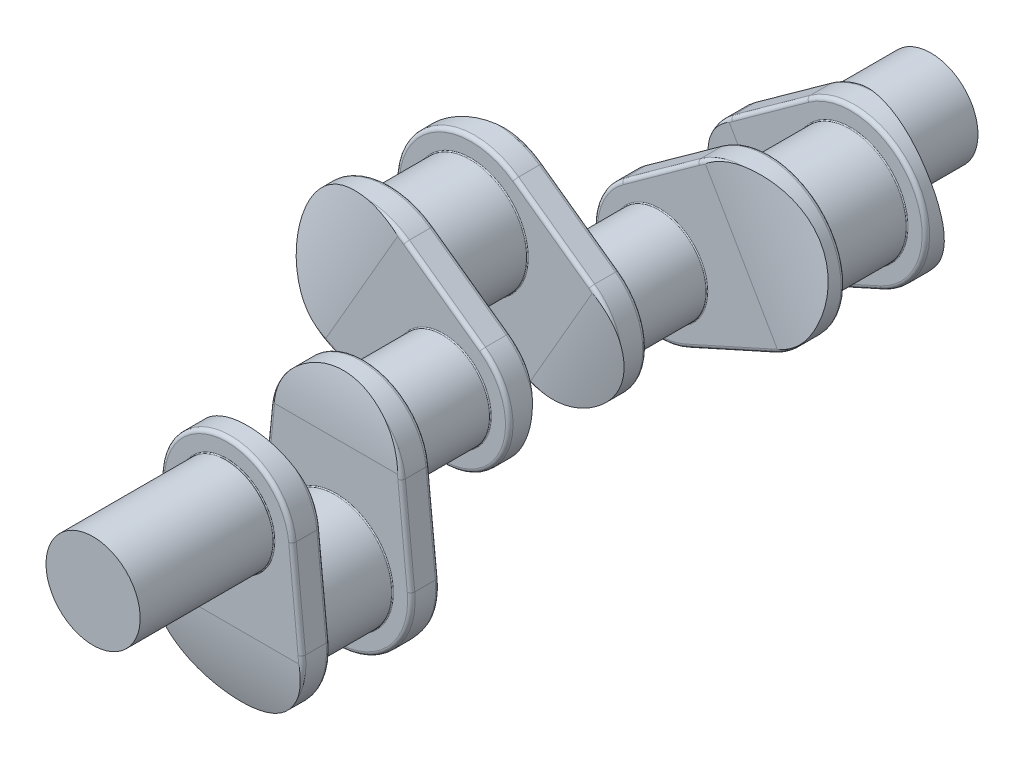
SolidWorks part; units mm, degrees
ref_plane "Front Plane" through (0, 0, 0) normal (0, 0, 1) x (1, 0, 0)
ref_plane "Top Plane" through (0, 0, 0) normal (0, 1, 0) x (1, 0, 0)
ref_plane "Right Plane" through (0, 0, 0) normal (1, 0, 0) x (0, 0, -1)
sketch "Sketch1" plane through (0, 0, 0) normal (0, 0, 1) x (1, 0, 0)
  circle A0 centre (0, 0) radius 38.1
  dimension "D1" = 76.2
extrude "Boss-Extrude1" add sketch "Sketch1" along normal blind 27.31
sketch "Sketch2" plane through (0, 0, 27.31) normal (0, 0, 1) x (1, 0, 0)
  line L0 (44.2272, 67.945) -> (50.5454, 5.08)
  line L1 (-44.2272, 67.945) -> (-50.5454, 5.08)
  arc A0 (-50.5454, 5.08) -> (50.5454, 5.08) centre (0, 0) ccw
  arc A1 (44.2272, 67.945) -> (-44.2272, 67.945) centre (0, 63.5) ccw
  circle A2 centre (0, 0) radius 38.1 construction
  point P11 (0, 0)
  dimension "D1" = 12.7
  dimension "D2" = 88.9
  dimension "D3" = 63.5
extrude "Boss-Extrude2" add sketch "Sketch2" along normal blind 19
sketch "Sketch3" plane through (0, 0, 46.31) normal (0, 0, 1) x (1, 0, 0)
  circle A0 centre (0, 63.5) radius 31.75
  dimension "D1" = 63.5
extrude "Boss-Extrude3" add sketch "Sketch3" along normal blind 26.67
sketch "Sketch4" plane through (0, 0, 0) normal (1, 0, 0) x (0, 0, -1)
  line L0 (-46.31, 0) -> (-27.31, 0) construction
  line L1 (-46.31, 5.08) -> (-46.31, -50.8) construction
  line L2 (-46.31, -50.8) -> (-27.31, -50.8) construction
  line L3 (-46.31, 0) -> (-60.4648, 0)
  line L4 (-60.4648, 0) -> (-60.4648, -50.8)
  line L5 (-60.4648, -50.8) -> (-36.81, -50.8)
  line L6 (-46.31, 63.5) -> (-27.31, 63.5) construction
  line L7 (-27.31, 107.95) -> (-46.31, 107.95) construction
  line L8 (-27.31, 67.945) -> (-27.31, 107.95) construction
  line L9 (-27.31, 63.5) -> (-17.3681, 63.5)
  line L10 (-17.3681, 63.5) -> (-17.3681, 107.95)
  line L11 (-17.3681, 107.95) -> (-32.31, 107.95)
  arc A0 (-46.31, 0) -> (-36.81, -50.8) centre (122.6069, 5.3005) ccw
  arc A1 (-27.31, 63.5) -> (-32.31, 107.95) centre (-196.2738, 67.0002) ccw
  dimension "D1" = 169
  dimension "D3" = 169
  dimension "D2" = 5
extrude "Cut-Extrude1" cut sketch "Sketch4" against normal through all both and the other way through all
fillet "Fillet1" radius 0.64 2 edges at (38.1, 0, 27.31) (31.75, 63.5, 46.31)
fillet "Fillet2" radius 2.54 10 edges at (50.7363, 2.5432, 46.31) (-50.7363, 2.5432, 46.31) (-47.3863, 36.5125, 46.31) (0, 107.95, 46.31) (-44.0798, 69.2251, 27.31) (-47.3863, 36.5125, 27.31) (0, -50.8, 27.31) (44.0798, 69.2251, 27.31) (47.3863, 36.5125, 46.31) (47.3863, 36.5125, 27.31)
mirror "Mirror2" about plane through (0, 0, 0) normal (0, 0, 1) of "Fillet2", "Fillet1", "Cut-Extrude1", "Boss-Extrude3", "Boss-Extrude2", "Boss-Extrude1"
pattern_linear "LPattern1" count 3 spacing 145.96 along (0, 0, -1) of bodies 117
ref_axis "Axis1" through (0, 63.5, 166.4472) along (0, 0, -1)
move or copy body "Body-Move/Copy1" bodies to move or copy 118 copy no rotation origin (0, 63.5, 0) rotation axis (0, 0, -1) rotation angle 120
move or copy body "Body-Move/Copy2" bodies to move or copy 119 copy no rotation origin (0, 63.5, 0) rotation axis (0, 0, 1) rotation angle 120
combine bodies "Combine1" operation type add bodies to combine 117 120 121
sketch "Sketch5" plane through (0, 0, 72.98) normal (0, 0, 1) x (1, 0, 0)
  circle A1 centre (0, 63.5) radius 31.75
  circle A2 centre (0, 63.5) radius 31.75
  dimension "D1" = 0
extrude "Boss-Extrude4" add sketch "Sketch5" along normal blind 63.5
sketch "Sketch6" plane through (0, 0, -364.9) normal (0, 0, -1) x (-1, 0, 0)
  circle A1 centre (0, 63.5) radius 31.75
  circle A2 centre (0, 63.5) radius 31.75
  dimension "D1" = 0
extrude "Boss-Extrude5" add sketch "Sketch6" along normal blind 63.5
